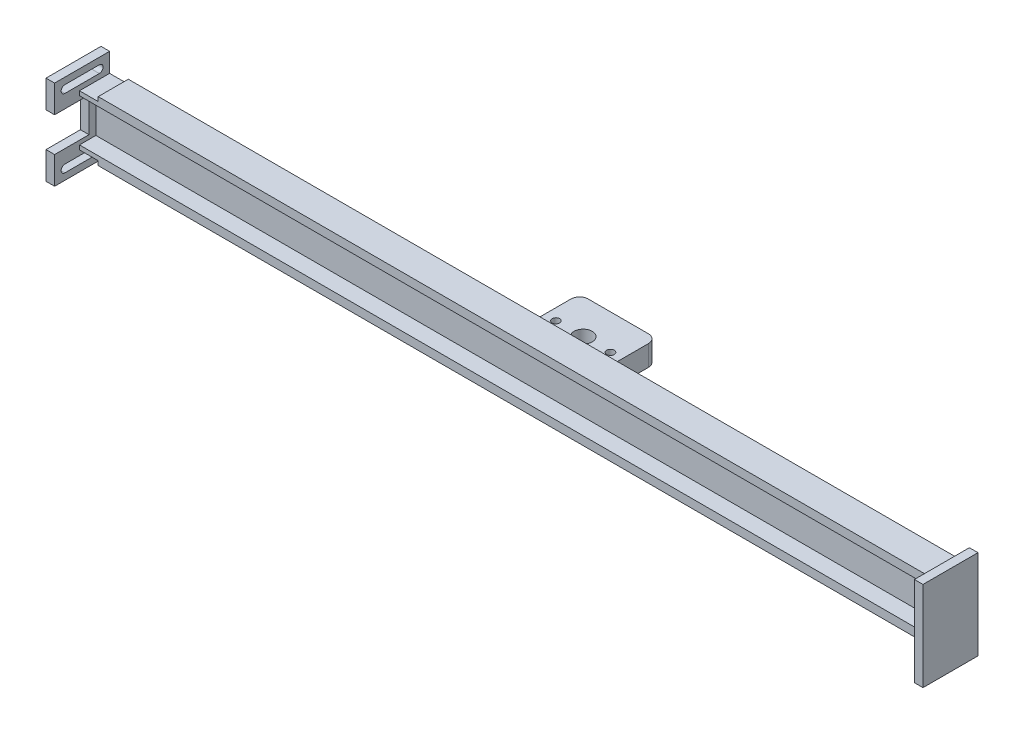
SolidWorks part; units mm, degrees
material "PLA"
ref_plane "Front Plane" through (0, 0, 0) normal (1, 0, 0) x (0, 1, 0)
ref_plane "Top Plane" through (0, 0, 0) normal (0, 0, 1) x (0, 1, 0)
ref_plane "Right Plane" through (0, 0, 0) normal (0, 1, 0) x (-1, 0, 0)
sketch "Sketch1" plane through (0, 0, 0) normal (1, 0, 0) x (0, 1, 0)
  line L16 (0, 4.7625) -> (-2.5, 4.7625)
  line L17 (0, 0) -> (12.3825, 0)
  line L18 (0, 0) -> (0, 4.7625)
  line L19 (0, 4.7625) -> (12.3825, 4.7625) construction
  line L20 (12.3825, 0) -> (12.3825, 4.7625)
  line L21 (-2.5, 4.7625) -> (-2.5, -4)
  line L22 (-2.5, -4) -> (14.8825, -4)
  line L23 (14.8825, -4) -> (14.8825, 4.7625)
  line L24 (12.3825, 4.7625) -> (14.8825, 4.7625)
  dimension "D1" = 4.7625
  dimension "D2" = 12.3825
  dimension "D3" = 2.5
extrude "Boss-Extrude1" add sketch "Sketch1" along normal blind 250
sketch "Sketch3" plane through (0, -2.5, 0) normal (0, -1, 0) x (1, 0, 0)
  line L0 (120.0194, -4) -> (129.9806, -4)
  line L1 (250, -4) -> (0, -4) construction
  line L2 (129.9806, -4) -> (129.9806, -9)
  line L3 (120.0194, -4) -> (120.0194, -10.1759)
  line L4 (0, 4.7625) -> (0, -4) construction
  arc A0 (120.0194, -10.1759) -> (129.9806, -9) centre (125.0694, -10.1759) ccw
  circle A1 centre (125.0694, -10.1759) radius 2.55
  point P5 (125, -4)
  dimension "D2" = 5.1
  dimension "D3" = 5
  dimension "D4" = 125
extrude "Boss-Extrude2" [suppressed] add sketch "Sketch3" against normal up to surface (17.3825 mm away) up to face at (125, 14.8825, 0.3813)
sketch "Sketch6" plane through (0, -2.5, 0) normal (0, -1, 0) x (1, 0, 0)
  line L0 (250, -4) -> (0, -4) construction
  line L1 (117.5385, -4) -> (131.3691, -4)
  line L2 (117.5385, -4) -> (117.5385, -13.6365)
  line L3 (117.5385, -13.6365) -> (131.3691, -13.6365)
  line L4 (131.3691, -4) -> (131.3691, -13.6365)
extrude "Cut-Extrude2" [suppressed] cut sketch "Sketch6" against normal blind 5
sketch "Sketch7" plane through (0, 14.8825, 0) normal (0, 1, 0) x (-1, 0, 0)
  line L0 (-250, -4) -> (0, -4) construction
  line L1 (-136.5723, -4) -> (-116.3235, -4)
  line L2 (-136.5723, -4) -> (-136.5723, -14.7915)
  line L3 (-136.5723, -14.7915) -> (-116.3235, -14.7915)
  line L4 (-116.3235, -4) -> (-116.3235, -14.7915)
extrude "Cut-Extrude3" [suppressed] cut sketch "Sketch7" against normal blind 5
sketch "Sketch8" [suppressed] plane through (250, 0, 0) normal (1, 0, 0) x (0, 1, 0)
  line L0 (6.1913, 0) -> (6.1913, -4) construction
  line L5 (12.3825, 0) -> (0, 0) construction
  line L6 (14.8825, -4) -> (-2.5, -4) construction
  line L11 (0, -3) -> (12.3825, -3)
  line L12 (0, -3) -> (0, -1)
  line L13 (0, -1) -> (12.3825, -1)
  line L14 (12.3825, -3) -> (12.3825, -1)
  line L15 (0, -3) -> (12.3825, -1) construction
  line L16 (0, -1) -> (12.3825, -3) construction
  point P6 (6.1913, -2)
  dimension "D1" = 12.3825
extrude "Cut-Extrude4" [suppressed] cut sketch "Sketch8" against normal through all
sketch "Sketch9" [suppressed] plane through (0, 0, -4) normal (0, 0, -1) x (-1, 0, 0)
  line L0 (-117.5194, -2.5) -> (-117.5194, 14.8825) construction
  line L1 (-120.0194, -2.5) -> (0, -2.5) construction
  line L2 (-120.0194, 14.8825) -> (0, 14.8825) construction
  line L3 (-120.0194, 14.8825) -> (-120.0194, -2.5) construction
  line L4 (-116.5194, 12.3825) -> (-118.5194, 12.3825)
  line L5 (-116.5194, 12.3825) -> (-116.5194, 0)
  line L6 (-116.5194, 0) -> (-118.5194, 0)
  line L7 (-118.5194, 12.3825) -> (-118.5194, 0)
  line L8 (-116.5194, 12.3825) -> (-118.5194, 0) construction
  line L9 (-116.5194, 0) -> (-118.5194, 12.3825) construction
  point P6 (-117.5194, 6.1913)
  dimension "D3" = 2.5
  dimension "D1" = 12.3825
extrude "Cut-Extrude5" [suppressed] cut sketch "Sketch9" against normal up to next
ref_plane "Plane1" through (125.0694, 0, 0) normal (-1, 0, 0) x (0, 0, 1)
mirror "Mirror1" [suppressed] about plane through (125.0694, 0, 0) normal (-1, 0, 0)
sketch "Sketch10" plane through (0, 0, 4.7625) normal (0, 0, 1) x (1, 0, 0)
  line L1 (0, 14.8825) -> (2.5, 14.8825)
  line L2 (0, 14.8825) -> (0, 18.8912)
  line L3 (0, 18.8912) -> (2.5, 18.8912)
  line L4 (2.5, 14.8825) -> (2.5, 18.8912)
  line L5 (0, -2.5) -> (2.5, -2.5)
  line L6 (0, -2.5) -> (0, -6.5088)
  line L7 (0, -6.5088) -> (2.5, -6.5088)
  line L8 (2.5, -2.5) -> (2.5, -6.5088)
  dimension "D2" = 25.4
extrude "Boss-Extrude3" [suppressed] add sketch "Sketch10" against normal up to surface (8.7625 mm away) up to face at (125, 6.1913, -4)
mirror "Mirror2" [suppressed] about plane through (125.0694, 0, 0) normal (-1, 0, 0)
sketch "Sketch11" [suppressed] plane through (250.1388, 0, 0) normal (1, 0, 0) x (0, 1, 0)
  circle A0 centre (16.3513, -1.46) radius 1.25 construction
  circle A1 centre (-3.9687, -1.46) radius 1.25 construction
  circle A2 centre (16.3513, -1.46) radius 1.25
  circle A3 centre (-3.9687, -1.46) radius 1.25
extrude "Cut-Extrude6" [suppressed] cut sketch "Sketch11" against normal up to surface (2.5 mm away)
mirror "Mirror3" [suppressed] about plane through (125.0694, 0, 0) normal (-1, 0, 0)
sketch "Sketch14" [suppressed] plane through (0, 0, 4.7625) normal (0, 0, 1) x (1, 0, 0)
  line L0 (0, 6.1912) -> (17.1619, 6.1912) construction
  line L1 (0, -6.5088) -> (3, -6.5088)
  line L2 (0, -6.5088) -> (0, -1.5088)
  line L3 (0, -1.5088) -> (3, -1.5088)
  line L4 (3, -6.5088) -> (3, -1.5088)
  line L5 (0, 12.3825) -> (0, 0) construction
  line L6 (0, 13.8912) -> (3, 13.8912)
  line L7 (3, 18.8912) -> (3, 13.8912)
  line L8 (0, 18.8912) -> (3, 18.8912)
  line L9 (0, 18.8912) -> (0, 13.8912)
  dimension "D2" = 3
extrude "Cut-Extrude7" [suppressed] cut sketch "Sketch14" against normal blind 4
mirror "Mirror4" [suppressed] about plane through (125.0694, 0, 0) normal (-1, 0, 0)
sketch "Sketch15" [suppressed] plane through (0, -2.5, 0) normal (0, -1, 0) x (-1, 0, 0)
  line L0 (-3, -0.7625) -> (-2.5, -0.7625) construction
  line L1 (-2.5, 4) -> (-6, 4)
  line L2 (-2.5, 4) -> (-2.5, -0.7625)
  line L3 (-2.5, -0.7625) -> (-6, -0.7625)
  line L4 (-6, 4) -> (-6, -0.7625)
  line L5 (0, 4) -> (0, -0.7625) construction
  dimension "D1" = 6
extrude "Cut-Extrude9" [suppressed] cut sketch "Sketch15" against normal blind 1 contours L4 L3 L2 L1
ref_plane "Plane3" through (0, 6.1913, 0) normal (0, 1, 0) x (1, 0, 0)
mirror "Mirror7" [suppressed] about plane through (0, 6.1913, 0) normal (0, 1, 0)
sketch "Sketch16" plane through (0, -2.5, 0) normal (0, -1, 0) x (1, 0, 0)
  line L0 (250, -4) -> (0, -4) construction
  line L1 (125, -4) -> (125, -29.4) construction
  line L2 (113.75, -4) -> (136.25, -4)
  line L3 (113.75, -4) -> (113.75, -29.4)
  line L4 (113.75, -29.4) -> (136.25, -29.4)
  line L5 (136.25, -4) -> (136.25, -29.4)
  line L6 (250, -4) -> (0, -4) construction
  line L7 (117.0625, -16.7) -> (132.9375, -16.7) construction
  circle A0 centre (117.0625, -16.7) radius 1.1
  circle A1 centre (132.9375, -16.7) radius 1.1
  circle A2 centre (125, -16.7) radius 2.65
  point P8 (125, -4)
  point P13 (125, -16.7)
  dimension "D4" = 2.2
  dimension "D5" = 2.2
  dimension "D6" = 5.3
  dimension "D2" = 15.875
  dimension "D3" = 22.5
  dimension "D1" = 12.7
extrude "Boss-Extrude4" add sketch "Sketch16" against normal blind 6
sketch "Sketch17" plane through (0, 0, -29.4) normal (0, 0, -1) x (1, 0, 0)
  line L4 (136.25, 2.5) -> (113.75, 2.5)
  line L5 (113.75, 2.5) -> (113.75, -3.5)
  line L6 (113.75, -3.5) -> (136.25, -3.5)
  line L7 (136.25, -3.5) -> (136.25, 2.5)
  line L8 (136.25, 2.5) -> (113.75, 2.5)
  line L9 (113.75, 2.5) -> (113.75, -3.5)
  line L10 (113.75, -3.5) -> (136.25, -3.5)
  line L11 (136.25, -3.5) -> (136.25, 2.5)
  dimension "D1" = 0
extrude "Cut-Extrude10" cut sketch "Sketch17" against normal blind 2.5
sketch "Sketch20" plane through (0, 0, 0) normal (-1, 0, 0) x (0, -1, 0)
  line L0 (2.5, -4) -> (-14.8825, -4) construction
  line L1 (-19.1913, -4) -> (6.8087, -4)
  line L2 (-19.1913, -4) -> (-19.1913, 12)
  line L3 (-19.1913, 12) -> (6.8087, 12)
  line L4 (6.8087, -4) -> (6.8087, 12)
  line L5 (-6.1913, 12) -> (-6.1913, -4) construction
  line L7 (-6.1913, 0) -> (-6.1913, -4) construction
  line L8 (-12.3825, 0) -> (0, 0) construction
  dimension "D1" = 26
  dimension "D2" = 16
extrude "Boss-Extrude7" add sketch "Sketch20" along normal blind 2.5
sketch "Sketch21" plane through (-2.5, 0, 0) normal (-1, 0, 0) x (0, -1, 0)
  line L0 (-6.1913, 12) -> (-6.1913, -4) construction
  line L1 (6.8087, 12) -> (-19.1913, 12) construction
  line L2 (-19.1913, -4) -> (6.8087, -4) construction
  line L3 (-16.1913, 9) -> (3.8087, 9) construction
  line L4 (-16.1913, 9) -> (-16.1913, -1) construction
  line L5 (-15.0913, 9) -> (-15.0913, -1)
  line L6 (-17.2913, 9) -> (-17.2913, -1)
  line L7 (3.8087, 9) -> (3.8088, -1) construction
  line L8 (2.7088, 9) -> (2.7088, -1)
  line L9 (4.9087, 9) -> (4.9087, -1)
  arc A2 (-15.0913, 9) -> (-17.2913, 9) centre (-16.1913, 9) ccw
  arc A3 (-17.2913, -1) -> (-15.0913, -1) centre (-16.1913, -1) ccw
  arc A4 (2.7088, 9) -> (4.9087, 9) centre (3.8087, 9) cw
  arc A5 (4.9087, -1) -> (2.7088, -1) centre (3.8088, -1) cw
  point P9 (-6.1913, 9)
  point P10 (-16.1913, 4)
  point P16 (3.8087, 4)
  dimension "D1" = 1.1
  dimension "D2" = 20
  dimension "D4" = 10
  dimension "D3" = 13
extrude "Cut-Extrude12" cut sketch "Sketch21" against normal blind 2.5
sketch "Sketch22" plane through (-2.5, 0, 0) normal (-1, 0, 0) x (0, -1, 0)
  line L0 (-6.1913, 12) -> (-6.1913, -4) construction
  line L1 (6.8087, 12) -> (-19.1913, 12) construction
  line L2 (-19.1913, -4) -> (6.8087, -4) construction
  line L4 (-11.1913, 2) -> (-1.1913, 2)
  line L5 (-11.1913, 2) -> (-11.1913, 12)
  line L6 (-11.1913, 12) -> (-1.1913, 12)
  line L7 (-1.1913, 2) -> (-1.1913, 12)
  line L8 (-11.1913, 2) -> (-1.1913, 12) construction
  line L9 (-11.1913, 12) -> (-1.1913, 2) construction
  point P6 (-6.1913, 7)
  dimension "D1" = 10
  dimension "D2" = 10
extrude "Cut-Extrude13" cut sketch "Sketch22" against normal blind 10
sketch "Sketch23" plane through (0, 14.8825, 0) normal (0, 1, 0) x (-1, 0, 0)
  line L0 (-250, -4) -> (0, -4) construction
  line L1 (0, 4.7625) -> (-5.4373, 4.7625)
  line L2 (0, 4.7625) -> (0, -4)
  line L3 (0, -4) -> (-5.4373, -4)
  line L4 (-5.4373, 4.7625) -> (-5.4373, -4)
extrude "Cut-Extrude14" cut sketch "Sketch23" against normal blind 1.25
mirror "Mirror8" about plane through (0, 6.1913, 0) normal (0, 1, 0) of "Cut-Extrude14"
sketch "Sketch24" plane through (250, 0, 0) normal (1, 0, 0) x (0, 1, 0)
  line L1 (-6.8087, -4) -> (19.1913, -4)
  line L2 (-6.8087, -4) -> (-6.8087, 12)
  line L3 (-6.8087, 12) -> (19.1913, 12)
  line L4 (19.1913, -4) -> (19.1913, 12)
extrude "Boss-Extrude8" add sketch "Sketch24" along normal blind 2.5
fillet "Fillet1" radius 2.5 2 edges at (136.25, 0.5, -26.9) (113.75, 0.5, -26.9)
sketch "Sketch25" plane through (-2.5, 0, 0) normal (-1, 0, 0) x (0, -1, 0)
  line L0 (-6.1913, 2) -> (-6.1913, -4) construction
  line L1 (-9.9413, -2.199) -> (-2.4413, -2.199)
  line L2 (-9.9413, -2.199) -> (-9.9413, -0.199)
  line L3 (-9.9413, -0.199) -> (-2.4413, -0.199)
  line L4 (-2.4413, -2.199) -> (-2.4413, -0.199)
  line L5 (-9.9413, -2.199) -> (-2.4413, -0.199) construction
  line L6 (-9.9413, -0.199) -> (-2.4413, -2.199) construction
  line L7 (-11.1913, 2) -> (-1.1913, 2) construction
  line L8 (-19.1913, -4) -> (6.8087, -4) construction
  point P0 (-6.1913, -1.199)
  dimension "D1" = 7.5
  dimension "D2" = 2
extrude "Cut-Extrude15" cut sketch "Sketch25" against normal blind 115
sketch "Sketch26" plane through (0, 0, -4) normal (0, 0, -1) x (1, 0, 0)
  line L0 (112.5, -2.4413) -> (-2.5, -2.4413) construction
  line L5 (105, -9.9413) -> (97.5, -9.9413)
  line L6 (105, -9.9413) -> (105, -2.4413)
  line L7 (105, -2.4413) -> (97.5, -2.4413)
  line L8 (97.5, -9.9413) -> (97.5, -2.4413)
  line L9 (-2.5, -19.1913) -> (-2.5, 6.8087) construction
  dimension "D1" = 100
  dimension "D2" = 7.5
  dimension "D3" = 7.5
extrude "Cut-Extrude17" cut sketch "Sketch26" against normal up to surface (1.801 mm away) contours L8 L7 L6 L5 up to face at (55, 6.1913, -2.199)
equation "\"D1@Sketch1\"=\"ball_diameter\" * 0.25"
equation "\"D2@Sketch1\"=\"ball_diameter\" * 0.65"
equation "\"D3@Sketch1\"=\"wall_thickness\""
equation "\"D4@Sketch1\"=0.4cm"
equation "\"D1@Boss-Extrude1\"=\"track_length\""
equation "\"D2@Sketch3\"=\"axle\" + 0.01"
equation "\"ball_diameter\"= 0.75in"
equation "\"wall_thickness\" = 0.25cm"
equation "\"track_length\" = 25cm"
equation "\"axle\" = 5mm"
equation "\"D3@Sketch3\"=\"axle\" * 1"
equation "\"D4@Sketch3\"=\"track_length\" / 2"
equation "\"pillar_width\" = 2.75cm"
equation "\"D1@Sketch9\"=\"ball_diameter\" * 0.65"
equation "\"D1@Sketch8\"=\"ball_diameter\"*0.65"
equation "\"D1@Sketch10\"=\"wall_thickness\""
equation "\"D2@Sketch14\"=0.3"
equation "\"D5@Sketch16\"=\"D4@Sketch16\""
